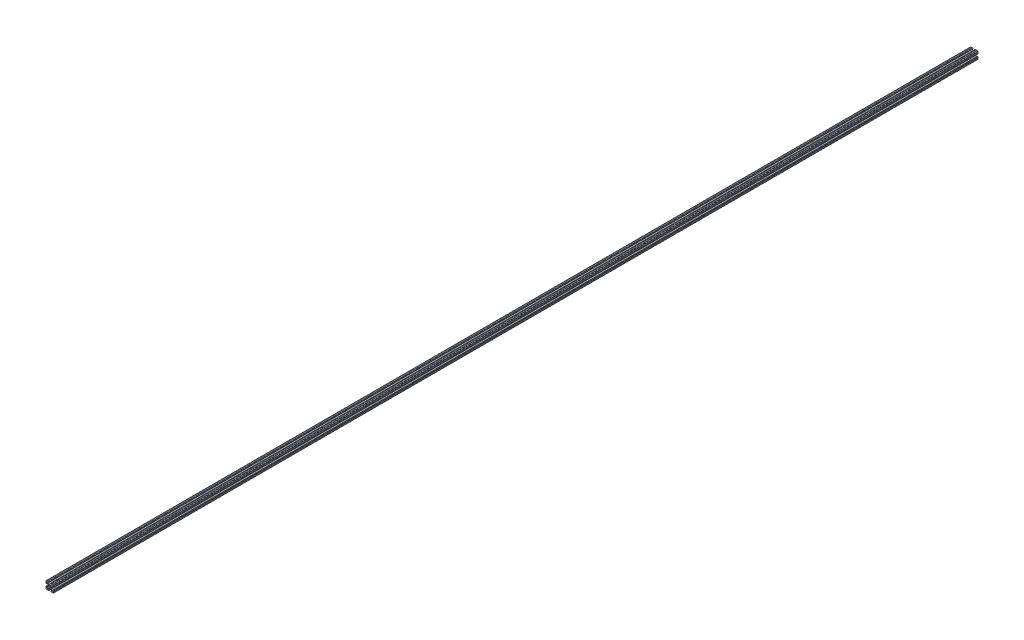
SolidWorks part; units mm, degrees
ref_plane "Front Plane" through (0, 0, 0) normal (0, 0, 1) x (1, 0, 0)
ref_plane "Top Plane" through (0, 0, 0) normal (0, 1, 0) x (1, 0, 0)
ref_plane "Right Plane" through (0, 0, 0) normal (1, 0, 0) x (0, 0, -1)
sketch "Sketch2" plane through (0, 0, 0) normal (0, 0, 1) x (1, 0, 0)
  line L0 (0, 12.7) -> (0, -12.7) construction
  line L1 (-12.7, 0) -> (12.7, 0) construction
  line L2 (3.2512, -12.7) -> (12.7, -12.7)
  line L3 (12.7, -12.7) -> (12.7, -3.2512)
  line L4 (3.2512, -12.7) -> (3.2512, -10.4902)
  line L5 (3.2512, -10.4902) -> (8.9276, -10.4902)
  line L6 (8.9276, -10.4902) -> (3.0856, -4.6482)
  line L7 (0, 0) -> (12.7, -12.7) construction
  line L8 (12.7, -3.2512) -> (10.4902, -3.2512)
  line L9 (10.4902, -3.2512) -> (10.4902, -8.9276)
  line L10 (10.4902, -8.9276) -> (4.6482, -3.0856)
  circle A0 centre (0, 0) radius 2.6035
  arc A1 (6.3485, -10.4902) -> (7.1039, -8.6665) centre (6.3485, -9.4219) ccw construction
  point P8 (0, -4.6482)
  dimension "Center Hole Diameter" = 5.207
  dimension "Rail Height" = 25.4
  dimension "Rail Width" = 25.4
  dimension "T-Slot Width" = 6.5024
  dimension "Slot Inner Width" = 14.8336
  dimension "Thickness" = 2.2098
  dimension "Slot Depth" = 5.842
  dimension "D1" = 2.2098
sketch "Sketch3" plane through (0, 0, 0) normal (1, 0, 0) x (0, 0, -1)
  line L0 (-1524, -12.7) -> (1524, -12.7) construction
  line L1 (-1498.6, 0) -> (1498.6, 0) construction
  dimension "Length" = 3048
  dimension "D1" = 25.4
sketch "Sketch4" plane through (0, 0, 0) normal (0, 0, 1) x (1, 0, 0)
  line L0 (4.1904, -12.7) -> (10.1173, -12.7)
  line L1 (3.2512, -12.7) -> (12.7, -12.7) construction
  line L2 (3.2512, -12.7) -> (3.2512, -10.4902) construction
  line L3 (3.2512, -10.4902) -> (8.9276, -10.4902) construction
  line L4 (3.2512, -11.4294) -> (3.2512, -11.7608)
  line L5 (4.1904, -10.4902) -> (6.3485, -10.4902)
  line L6 (0, -4.6482) -> (2.164, -4.6482)
  line L7 (8.9276, -10.4902) -> (3.0856, -4.6482) construction
  line L8 (3.7373, -5.2999) -> (7.1039, -8.6665)
  line L9 (12.7, -12.7) -> (12.7, -3.2512) construction
  line L10 (10.4902, -8.9276) -> (4.6482, -3.0856) construction
  line L11 (10.4902, -3.2512) -> (10.4902, -8.9276) construction
  line L12 (10.4902, -6.3485) -> (10.4902, -4.1904)
  line L13 (12.7, -3.2512) -> (10.4902, -3.2512) construction
  line L14 (11.4294, -3.2512) -> (11.7608, -3.2512)
  line L15 (12.7, -4.1904) -> (12.7, -10.1173)
  line L16 (8.6665, -7.1039) -> (5.2999, -3.7373)
  line L17 (4.6482, 0) -> (4.6482, -2.164)
  line L18 (-12.7, 0) -> (12.7, 0) construction
  line L19 (0, -4.6482) -> (0, -2.6035)
  line L20 (0, 12.7) -> (0, -12.7) construction
  line L21 (4.6482, 0) -> (2.6035, 0)
  arc A0 (3.2512, -11.7608) -> (4.1904, -12.7) centre (4.1904, -11.7608) ccw
  arc A2 (3.2512, -11.4294) -> (4.1904, -10.4902) centre (4.1904, -11.4294) cw
  arc A3 (6.3485, -10.4902) -> (7.1039, -8.6665) centre (6.3485, -9.4219) ccw
  arc A4 (2.164, -4.6482) -> (3.7373, -5.2999) centre (2.164, -6.8732) cw
  arc A5 (10.1173, -12.7) -> (12.7, -10.1173) centre (10.1173, -10.1173) ccw
  arc A6 (8.6665, -7.1039) -> (10.4902, -6.3485) centre (9.4219, -6.3485) ccw
  arc A7 (10.4902, -4.1904) -> (11.4294, -3.2512) centre (11.4294, -4.1904) cw
  arc A8 (11.7608, -3.2512) -> (12.7, -4.1904) centre (11.7608, -4.1904) cw
  arc A9 (5.2999, -3.7373) -> (4.6482, -2.164) centre (6.8732, -2.164) cw
  circle A10 centre (0, 0) radius 2.6035 construction
  arc A11 (0, -2.6035) -> (2.6035, 0) centre (0, 0) ccw
  dimension "D1" = 2.5827
  dimension "D2" = 2.225
  dimension "D3" = 0.9392
extrude "Boss-Extrude1" add sketch "Sketch4" along normal mid plane 3048
sketch "Sketch5" plane through (0, 0, 0) normal (0, 0, 1) x (1, 0, 0)
  line L0 (3.2512, -12.7) -> (12.7, -12.7) construction
  line L1 (4.1904, -10.4902) -> (6.3485, -10.4902) construction
  line L3 (0, 0) -> (12.7, -12.7) construction
  line L4 (6.3485, -10.4902) -> (6.3485, -12.7) construction
  line L5 (8.9276, -10.4902) -> (3.0856, -4.6482) construction
  circle A0 centre (10.3562, -12.7) radius 0.5524
  circle A1 centre (5.796, -12.7) radius 0.5524
  circle A2 centre (12.7, -10.3562) radius 0.5524
  circle A3 centre (12.7, -5.796) radius 0.5524
  point P10 (5.2694, -10.4902)
  point P12 (9.4219, -6.3485)
  dimension "D1" = 1.1049
extrude "Cut-Extrude1" cut sketch "Sketch5" against normal through all both and the other way through all
mirror "Mirror1" about plane through (0, 0, 0) normal (1, 0, 0) of bodies 137 134
mirror "Mirror2" about plane through (0, 0, 0) normal (0, 1, 0) of bodies 135
equation "\"D1@Boss-Extrude1\"=\"Length@Sketch3\""
equation "\"D1@Sketch2\"=\"Thickness@Sketch2\""
equation "\"D2@Sketch4\"=\"Slot Inner Width@Sketch2\"*0.15"
equation "\"D1@Sketch4\"=\"D3@Sketch4\"*2.75"
equation "\"D3@Sketch4\"=\"Thickness@Sketch2\"*0.425"
equation "\"D1@Sketch5\"=\"Thickness@Sketch2\"*0.5"
